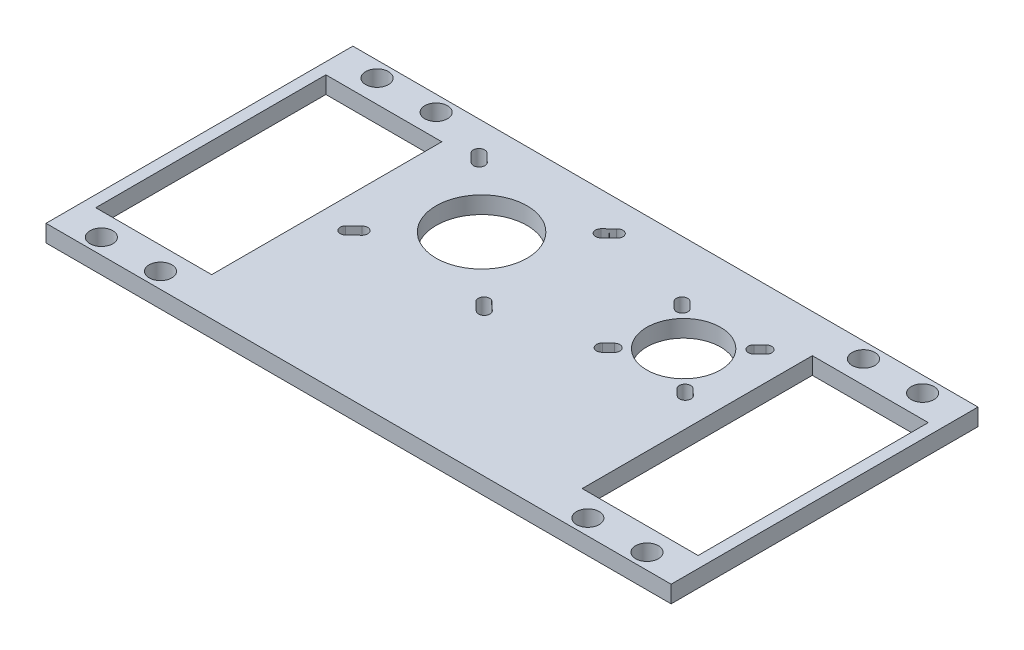
SolidWorks part; units mm, degrees
ref_plane "Plan de face" through (0, 0, 0) normal (0, 0, 1) x (1, 0, 0)
ref_plane "Plan de dessus" through (0, 0, 0) normal (0, 1, 0) x (1, 0, 0)
ref_plane "Plan de droite" through (0, 0, 0) normal (1, 0, 0) x (0, 0, -1)
sketch "Esquisse1" plane through (0, 0, 0) normal (0, 1, 0) x (1, 0, 0)
  line L1 (-54, 35.0217) -> (56, 35.0217)
  line L2 (-54, 35.0217) -> (-54, -18.9783)
  line L3 (-54, -18.9783) -> (56, -18.9783)
  line L4 (56, 35.0217) -> (56, -18.9783)
  dimension "D1" = 54
  dimension "D2" = 110
extrude "Boss.-Extru.1" add sketch "Esquisse1" along normal blind 3
sketch "Esquisse2" plane through (0, 3, 0) normal (0, 1, 0) x (1, 0, 0)
  line L0 (56, 35.0217) -> (-54, 35.0217) construction
  line L1 (-52, 28.2717) -> (-31.6, 28.2717)
  line L2 (-52, 28.2717) -> (-52, -12.2283)
  line L3 (-52, -12.2283) -> (-31.6, -12.2283)
  line L4 (-31.6, 28.2717) -> (-31.6, -12.2283)
  line L6 (-54, 35.0217) -> (-54, -18.9783) construction
  line L7 (33.6, 28.2717) -> (54, 28.2717)
  line L8 (33.6, 28.2717) -> (33.6, -12.2283)
  line L9 (33.6, -12.2283) -> (54, -12.2283)
  line L10 (54, 28.2717) -> (54, -12.2283)
  line L11 (56, -18.9783) -> (56, 35.0217) construction
  circle A0 centre (-47, 32.2717) radius 2
  circle A1 centre (-36.6, 32.2717) radius 2
  circle A2 centre (-47, -16.2283) radius 2
  circle A3 centre (-36.6, -16.2283) radius 2
  circle A4 centre (38.6, 32.2717) radius 2
  circle A5 centre (49, 32.2717) radius 2
  circle A6 centre (38.6, -16.2283) radius 2
  circle A7 centre (49, -16.2283) radius 2
  point P16 (-47.2617, 31.0715)
  point P17 (-36.9364, 31.0715)
  point P18 (0, 0)
  dimension "D7" = 4
  dimension "D8" = 4
  dimension "D9" = 4
  dimension "D10" = 4
  dimension "D21" = 4
  dimension "D22" = 4
  dimension "D23" = 4
  dimension "D24" = 4
  dimension "D1" = 40.5
  dimension "D2" = 20.4
  dimension "D3" = 6.75
  dimension "D4" = 2
  dimension "D5" = 4
  dimension "D6" = 4
  dimension "D11" = 4
  dimension "D12" = 4
  dimension "D13" = 5
  dimension "D14" = 5
  dimension "D15" = 5
  dimension "D16" = 5
  dimension "D17" = 40.5
  dimension "D18" = 20.4
  dimension "D19" = 4
  dimension "D20" = 4
  dimension "D25" = 4
  dimension "D26" = 4
  dimension "D27" = 5
  dimension "D28" = 5
  dimension "D29" = 5
  dimension "D30" = 5
  dimension "D31" = 2
  dimension "D32" = 6.75
extrude "Enlèv. mat.-Extru.1" cut sketch "Esquisse2" against normal blind 46
sketch "Esquisse3" plane through (0, 3, 0) normal (0, 1, 0) x (1, 0, 0)
  line L0 (-4.2842, 6.9571) -> (-2.7941, 5.5204)
  line L5 (28.6, 25.1266) -> (27.518, 24.0877) construction
  line L6 (-41.8001, 18.0218) -> (43.7999, 18.0218) construction
  line L7 (29.2926, 24.4052) -> (28.2105, 23.3664)
  line L8 (-4.3393, 29.0362) -> (-2.9466, 30.3684)
  line L9 (-2.9466, 29.0852) -> (-2.9466, 29.0788)
  line L10 (-2.9466, 27.6021) -> (-1.4865, 29.0059)
  line L11 (33.6, 28.2717) -> (33.6, -12.2283) construction
  line L12 (-25.9157, 5.5204) -> (-24.3881, 6.9802)
  line L13 (-1.4068, 6.9611) -> (-2.8532, 8.3521)
  line L14 (-2.1, 6.2403) -> (-1.3792, 5.5471)
  line L15 (-25.7698, 6.9802) -> (-25.7722, 6.9802)
  line L16 (-27.2687, 6.9802) -> (-25.7698, 8.4262)
  line L17 (11.8, 27.0468) -> (30.6, 8.9968)
  line L18 (-27.2932, 29.0825) -> (-25.8517, 27.6962)
  line L19 (-25.8869, 29.1021) -> (-25.8873, 29.1178)
  line L20 (-25.9229, 30.5392) -> (-24.4654, 29.1378)
  line L21 (11.8, 27.0468) -> (30.6, 27.0468)
  line L22 (-25.8873, 29.1178) -> (-25.8792, 29.1101)
  line L23 (11.8, 27.0468) -> (11.8, 8.9968)
  line L24 (11.8, 8.9968) -> (30.6, 8.9968)
  line L25 (30.6, 27.0468) -> (30.6, 8.9968)
  line L26 (11.8, 8.9968) -> (30.6, 27.0468)
  line L27 (27.9074, 25.8479) -> (26.8254, 24.8091)
  line L28 (28.5169, 10.9968) -> (27.4349, 12.0357) construction
  line L29 (27.8243, 10.2755) -> (26.7423, 11.3143)
  line L30 (29.2095, 11.7182) -> (28.1274, 12.757)
  line L31 (13.8831, 10.9968) -> (14.9651, 12.0357) construction
  line L32 (13.1905, 11.7182) -> (14.2726, 12.757)
  line L33 (14.5757, 10.2755) -> (15.6577, 11.3143)
  line L34 (13.8831, 25.0468) -> (14.9651, 24.0079) construction
  line L35 (14.5757, 25.7682) -> (15.6577, 24.7293)
  line L36 (13.1905, 24.3255) -> (14.2726, 23.2866)
  circle A0 centre (-14.35, 18.0218) radius 8
  arc A1 (-2.7941, 5.5204) -> (-1.4068, 6.9611) centre (-2.1, 6.2403) ccw
  arc A2 (-2.9466, 29.0852) -> (-2.9003, 29.0336) centre (-2.1795, 29.7268) ccw
  arc A3 (-27.1565, 7.0884) -> (-25.7523, 5.6765) centre (-26.5205, 6.3168) ccw
  arc A4 (-25.8869, 29.1022) -> (-25.8792, 29.1101) centre (-26.6, 29.8033) ccw
  arc A5 (-25.8517, 27.6962) -> (-24.4654, 29.1378) centre (-25.1585, 28.4169) ccw
  arc A7 (-4.2842, 29.0889) -> (-2.9098, 27.6375) centre (-3.621, 28.3404) ccw
  arc A8 (-2.8435, 8.3428) -> (-4.1835, 6.86) centre (-3.5415, 7.6267) ccw
  arc A9 (-1.4865, 29.0059) -> (-2.9466, 30.3684) centre (-2.1795, 29.7268) ccw
  arc A10 (-2.9003, 29.0336) -> (-2.9466, 29.0788) centre (-3.621, 28.3404) ccw
  arc A11 (-24.3881, 6.9802) -> (-25.7766, 8.4196) centre (-25.079, 7.7032) ccw
  arc A12 (-25.8792, 29.1101) -> (-25.8869, 29.1021) centre (-25.1585, 28.4169) ccw
  arc A13 (-25.8912, 30.5087) -> (-27.2932, 29.0825) centre (-26.6, 29.8033) ccw
  circle A14 centre (21.2, 18.0218) radius 6.5
  arc A15 (29.2926, 24.4052) -> (27.9074, 25.8479) centre (28.6, 25.1266) ccw
  arc A16 (26.8254, 24.8091) -> (28.2105, 23.3664) centre (27.518, 24.0877) ccw
  arc A17 (27.8243, 10.2755) -> (29.2095, 11.7182) centre (28.5169, 10.9968) ccw
  arc A18 (28.1274, 12.757) -> (26.7423, 11.3143) centre (27.4349, 12.0357) ccw
  arc A19 (13.1905, 11.7182) -> (14.5757, 10.2755) centre (13.8831, 10.9968) ccw
  arc A20 (15.6577, 11.3143) -> (14.2726, 12.757) centre (14.9651, 12.0357) ccw
  arc A21 (14.5757, 25.7682) -> (13.1905, 24.3255) centre (13.8831, 25.0468) ccw
  arc A22 (14.2726, 23.2866) -> (15.6577, 24.7293) centre (14.9651, 24.0079) ccw
  point P6 (28.059, 24.6072)
  point P63 (27.9759, 11.5162)
  point P70 (14.4241, 11.5162)
  point P75 (14.4241, 24.5274)
  dimension "D5" = 16
  dimension "D10" = 2
  dimension "D11" = 2
  dimension "D12" = 2
  dimension "D13" = 2
  dimension "D14" = 1
  dimension "D15" = 2
  dimension "D16" = 2
  dimension "D17" = 2
  dimension "D18" = 2
  dimension "D2" = 13
  dimension "D3" = 12.4
  dimension "D7" = 1
  dimension "D20" = 1
  dimension "D21" = 1
  dimension "D4" = 18.8
  dimension "D6" = 18.05
  dimension "D8" = 1.5
  dimension "D9" = 2
  dimension "D19" = 1.5
  dimension "D22" = 1.5
  dimension "D23" = 1.5
  dimension "D24" = 2
  dimension "D25" = 2
extrude "Enlèv. mat.-Extru.2" cut sketch "Esquisse3" against normal blind 10 contours L10 A9 L8 A7 A2 A10 L9 | A0 | L20 A13 L18 A5 L22 A12 L19 | L12 A11 L16 A3 | L13 A8 L0 A1 region at (-2.8204, 3, -6.9337) region at (-2.8998, 3, -29.0329) region at (-25.7997, 3, -7.0107) region at (-25.8793, 3, -29.1101) region at (-14.35, 3, -18.0218)
extrude "Enlèv. mat.-Extru.3" cut sketch "Esquisse3<3>" against normal blind 15 contours L17 A22 L35 A21 | L36 A22 L17 A21 | L27 A16 L26 A15 | L26 A16 L7 A15 | L26 A20 L32 A19 | L33 A20 L26 A19 | L30 A18 L17 A17 | L17 A18 L29 A17 | A14 region at (28.3785, 3, -24.2744) region at (27.7395, 3, -24.9399) region at (14.7436, 3, -24.8602) region at (14.1046, 3, -24.1946) region at (27.6564, 3, -11.1835) region at (28.2954, 3, -11.849) region at (14.1046, 3, -11.849) region at (14.7436, 3, -11.1835)
sketch "Esquisse3<3>" plane through (0, 3, 0) normal (0, 1, 0) x (1, 0, 0) same geometry as "Esquisse3"
